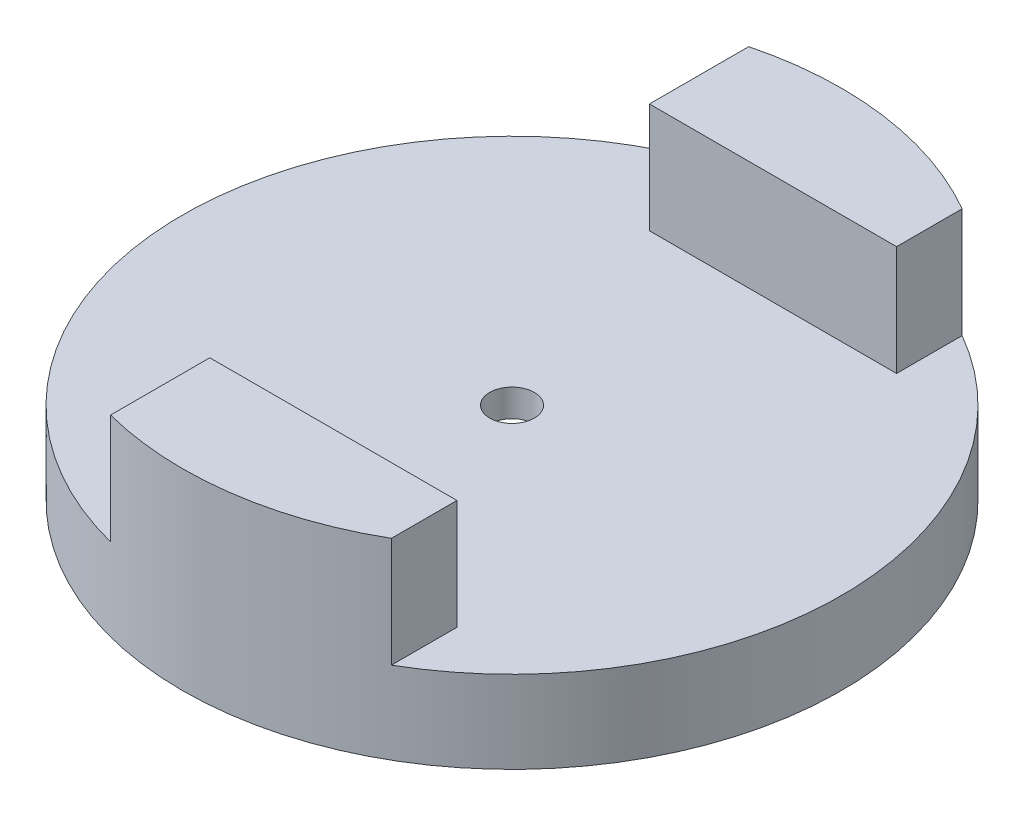
SolidWorks part; units mm, degrees
material "1023 Carbon Steel Sheet (SS)"
ref_plane "Front Plane" through (0, 0, 0) normal (0, 0, 1) x (1, 0, 0)
ref_plane "Top Plane" through (0, 0, 0) normal (0, 1, 0) x (1, 0, 0)
ref_plane "Right Plane" through (0, 0, 0) normal (1, 0, 0) x (0, 0, -1)
sketch "Sketch1" plane through (0, 0, 0) normal (0, 1, 0) x (1, 0, 0)
  line L0 (-19.05, -73.7803) -> (-19.05, -50.8305)
  line L1 (-19.05, -50.8305) -> (38.1, -50.8305)
  line L2 (38.1, -50.8305) -> (38.1, -65.9911)
  line L3 (0, 0) -> (-76.2, 0) construction
  line L4 (38.1, 50.8305) -> (38.1, 65.9911)
  line L5 (-19.05, 50.8305) -> (38.1, 50.8305)
  line L6 (-19.05, 73.7803) -> (-19.05, 50.8305)
  line L7 (-19.05, -63.5305) -> (38.1, -63.5305) construction
  line L8 (0, 0) -> (0, -63.5305) construction
  circle A0 centre (0, 0) radius 76.2
  circle A1 centre (0, 0) radius 74.1401
  circle A2 centre (0, 0) radius 5.1594
  dimension "D1" = 152.4
  dimension "D2" = 148.2801
  dimension "D6" = 10.3187
  dimension "D4" = 63.5305
  dimension "D5" = 12.7
  dimension "D7" = 19.05
  dimension "D3" = 38.1
extrude "Boss-Extrude1" add sketch "Sketch1" against normal blind 6.35 contours L2 A1 L4 L5 L6 L0 L1 | A1 L6 A0 L0 | A1 L0 A0 L2 | L0 A1 L2 L1 | L4 A1 L6 L5 | A1 L4 A0 L6 region at (-74.6176, 0, 0) region at (-18.4648, 0, 72.7156) region at (-72.078, 0, 0) region at (7.7413, 0, 61.4073) region at (10.2114, 0, -74.9221) region at (7.7413, 0, -61.4073)
extrude "Boss-Extrude2" add sketch "Sketch1<3>" against normal blind 19.05 contours A1 L6 A0 L0 | A1 L4 A0 L6 | A1 L2 A0 L4 | A1 L0 A0 L2 region at (-74.6176, 0, 0) region at (-18.4648, 0, 72.7156) region at (10.2114, 0, -74.9221) region at (39.4737, 0, 64.7963)
sketch "Sketch1<3>" plane through (0, 0, 0) normal (0, 1, 0) x (1, 0, 0) same geometry as "Sketch1"
extrude "Boss-Extrude3" add sketch "Sketch1<4>" along normal blind 25.4 contours A1 L4 A0 L6 | L4 A1 L6 L5 | L0 A1 L2 L1 | A1 L0 A0 L2 region at (-18.4648, 0, 72.7156) region at (7.7413, 0, 61.4073) region at (10.2114, 0, -74.9221) region at (7.7413, 0, -61.4073)
sketch "Sketch1<4>" plane through (0, 0, 0) normal (0, 1, 0) x (1, 0, 0) same geometry as "Sketch1"
hole_wizard "Pipe Tap Drill for 3/8 Tap1" positions "3DSketch1" profile "Sketch4" hole size "3/8" standard "ANSI Inch"
sketch3d "3DSketch1"
  line L0 (-19.05, 12.7, -63.5305) -> (-19.05, 12.7, -50.8305) construction
  line L1 (-19.05, 25.4, -50.8305) -> (-19.05, 0, -50.8305) construction
  line L3 (-19.05, 12.7, 50.8305) -> (-19.05, 12.7, 63.5305) construction
  line L4 (-19.05, 25.4, 50.8305) -> (-19.05, 0, 50.8305) construction
  point P0 (-19.05, 12.7, -63.5305)
  point P2 (-19.05, 12.7, 63.5305)
  dimension "D1" = 12.7
sketch "Sketch4" plane through (-19.05, 12.7, -63.5305) normal (0, 1, 0) x (0, 0, 1)
  line L0 (0, 0) -> (0, 34.7686)
  line L1 (0, 34.7686) -> (7.1374, 30.48)
  line L2 (7.1374, 30.48) -> (7.1374, 0)
  line L5 (7.1374, 0) -> (0, 0)
  line L10 (0, 34.7686) -> (-7.1374, 30.48) construction
  line L11 (0, -6.35) -> (0, 107.95) construction
  dimension "Hole Dia." = 14.2748
  dimension "Hole Depth" = 30.48
  dimension "Drill Angle" = 118
ref_plane "Plane1" through (0, 0, 63.5) normal (0, 0, 1) x (1, 0, 0)
sketch "Sketch5" plane through (0, 0, 63.5) normal (0, 0, 1) x (1, 0, 0)
  line L0 (-14.3299, -9.0101) -> (-0.5867, 0.4612)
  line L1 (-0.5867, 0.4612) -> (8.1444, 11.5673)
  line L2 (8.1444, 11.5673) -> (9.3178, 10.6449)
  line L3 (9.3178, 10.6449) -> (0.5867, -0.4612)
  line L4 (0.5867, -0.4612) -> (-5.3726, -16.0519)
  line L5 (-5.3726, -16.0519) -> (-14.3299, -9.0101)
  line L6 (-9.8513, -12.531) -> (8.7311, 11.1061)
  line L7 (-0.5867, 0.4612) -> (0.5867, -0.4612) construction
  point P8 (0, 0)
  point P9 (-9.6261, -3.4861)
  point P11 (-6.9184, -4.2204)
  point P12 (-13.2946, -10.6781)
  point P13 (-14.3299, -9.0101)
revolve "Cut-Revolve1" cut sketch "Sketch5" angle 360 about L6 region at (-7.7027, -6.6788, 63.5) region at (4.0722, 5.7837, 63.5)
equation "\"D2@Sketch1\"=2*(\"rotor tip@[TP] [Turb] Turbine.Assembly\"+\"rotor clearance@[TP] [Turb] Turbine.Assembly\")"
equation "\"D4@Sketch1\"=\"rotor pitchline@[TP] [Turb] Turbine.Assembly\""
